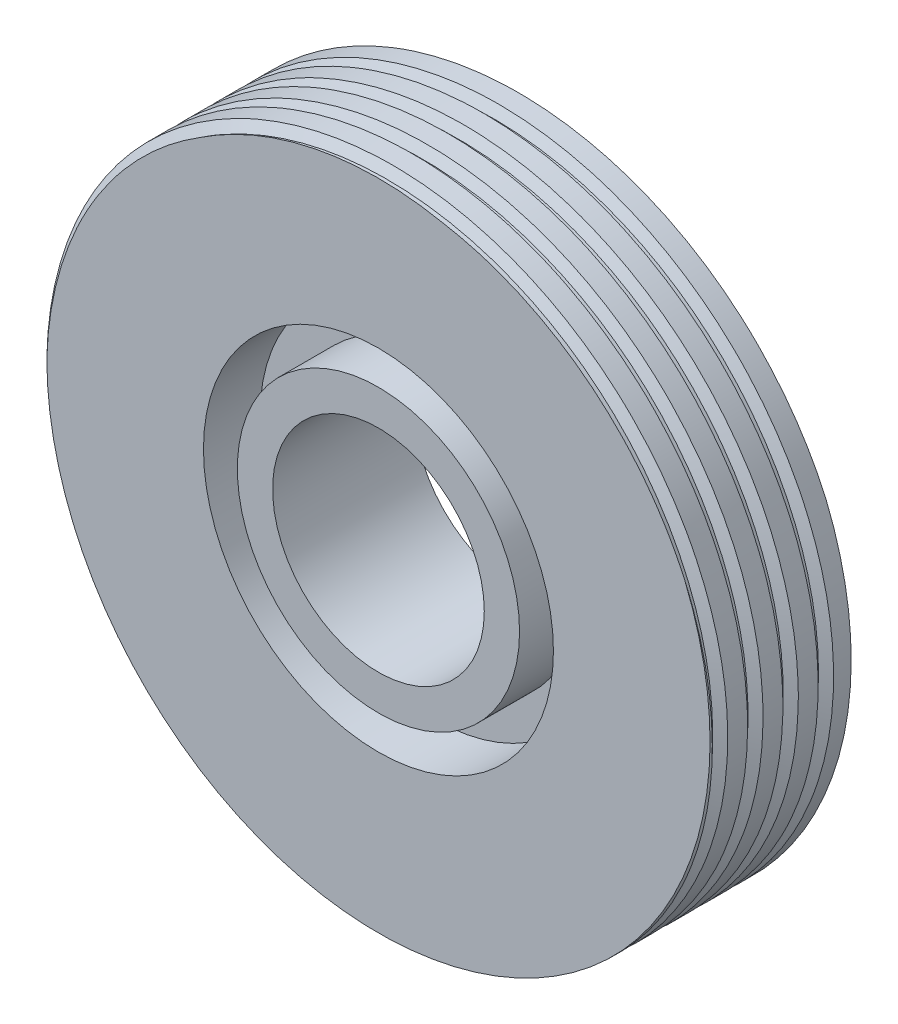
SolidWorks part; units mm, degrees
ref_plane "Front Plane" through (0, 0, 0) normal (0, 0, 1) x (1, 0, 0)
ref_plane "Top Plane" through (0, 0, 0) normal (0, 1, 0) x (1, 0, 0)
ref_plane "Right Plane" through (0, 0, 0) normal (1, 0, 0) x (0, 0, -1)
sketch "Sketch3" plane through (0, 0, 0) normal (0, 0, 1) x (1, 0, 0)
  circle A3 centre (8.3476, 27.7238) radius 14.9225
  dimension "D1" = 29.845
extrude "Boss-Extrude1" add sketch "Sketch3" against normal blind 6.35 contours A3 region at (8.3476, 27.7238, 0)
sketch "Sketch11" plane through (0, 0, 0) normal (0, 0, 1) x (1, 0, 0)
  circle A0 centre (8.3476, 27.7238) radius 4.7625
extrude "Cut-Extrude3" cut sketch "Sketch11" against normal through all
sketch "Sketch12" plane through (0, 0, 0) normal (0, 0, 1) x (1, 0, 0)
  circle A0 centre (8.3476, 27.7238) radius 6.35
  circle A1 centre (8.3476, 27.7238) radius 7.874
  dimension "D1" = 15.748
  dimension "D2" = 1.524
extrude "Cut-Extrude4" cut sketch "Sketch12" against normal blind 2.54
thread "Thread1" pitch 0.7937 method cut profile "Thread Profile1" start angle 0, offset 0.7937, length 7.62, pitch 1.5875, diameter 29.845
ref_plane "Plane1" through (23.2701, 27.7238, -7.1437) normal (0, -1, 0) x (1, 0, 0)
sketch "Thread Profile1" plane through (23.2701, 27.7238, -7.1437) normal (0, -1, 0) x (1, 0, 0)
  line L0 (0, 0) -> (0, 0.7937) construction
  line L11 (0, 0) -> (0, 0.6945)
  line L12 (0, 0.6945) -> (-0.4296, 0.4465)
  line L13 (-0.4296, 0.4465) -> (-0.4296, 0.248)
  line L15 (-0.4296, 0.248) -> (0, 0)
  line L17 (-0.4296, 0.3473) -> (0, 0.3473) construction
  point P2 (0, 0)
  dimension "Pitch" = 0.7937
  dimension "Profile_Angle" = 60
  dimension "Profile_Land" = 0.1984
  dimension "Profile_Height" = 0.4296
